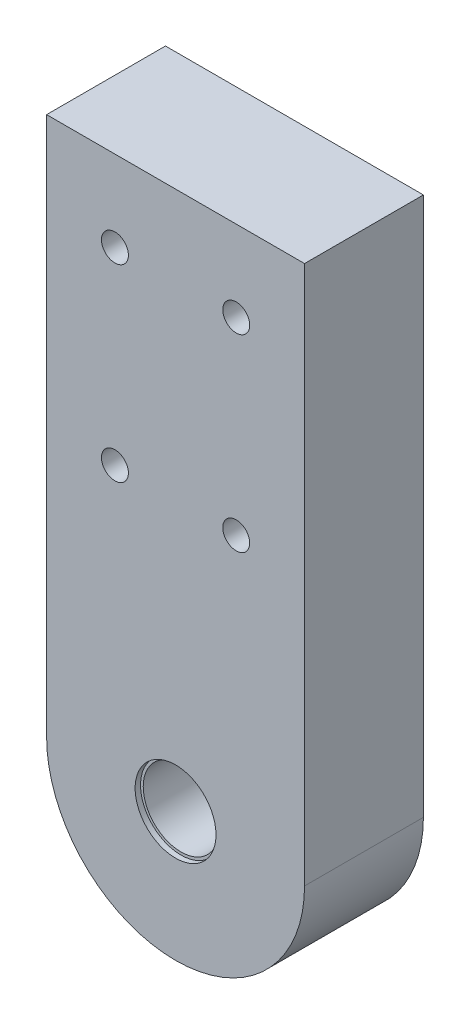
SolidWorks part; units mm, degrees
ref_plane "Front Plane" through (0, 0, 0) normal (0, 0, 1) x (1, 0, 0)
ref_plane "Top Plane" through (0, 0, 0) normal (0, 1, 0) x (1, 0, 0)
ref_plane "Right Plane" through (0, 0, 0) normal (1, 0, 0) x (0, 0, -1)
sketch "Sketch1" plane through (0, 0, 0) normal (0, 0, 1) x (1, 0, 0)
  line L0 (-23.925, 0) -> (-23.925, 100)
  line L1 (-23.925, 100) -> (23.925, 100)
  line L2 (23.925, 100) -> (23.925, 0)
  line L4 (-11.25, 85) -> (11.25, 85) construction
  line L5 (-11.25, 85) -> (-11.25, 50) construction
  line L6 (-11.25, 50) -> (11.25, 50) construction
  line L7 (11.25, 85) -> (11.25, 50) construction
  circle A0 centre (0, 0) radius 7
  arc A1 (-23.925, 0) -> (23.925, 0) centre (0, 0) ccw
  circle A2 centre (-11.25, 85) radius 2.5
  circle A3 centre (11.25, 85) radius 2.5
  circle A4 centre (11.25, 50) radius 2.5
  circle A5 centre (-11.25, 50) radius 2.5
  point P13 (0, 50)
  dimension "D1" = 14
  dimension "D4" = 5
  dimension "D2" = 47.85
  dimension "D3" = 100
  dimension "D5" = 35
  dimension "D6" = 15
  dimension "D7" = 22.5
extrude "Boss-Extrude1" add sketch "Sketch1" along normal blind 22.05
sketch "Sketch2" plane through (0, 0, 22.05) normal (0, 0, 1) x (1, 0, 0)
  circle A0 centre (0, 0) radius 7.5
  dimension "D1" = 15
extrude "Cut-Extrude1" cut sketch "Sketch2" against normal blind 1
sketch "Sketch3" plane through (0, 0, 0) normal (0, 0, -1) x (-1, 0, 0)
  circle A0 centre (0, 0) radius 7.5
  dimension "D1" = 15
extrude "Cut-Extrude2" cut sketch "Sketch3" against normal blind 1
